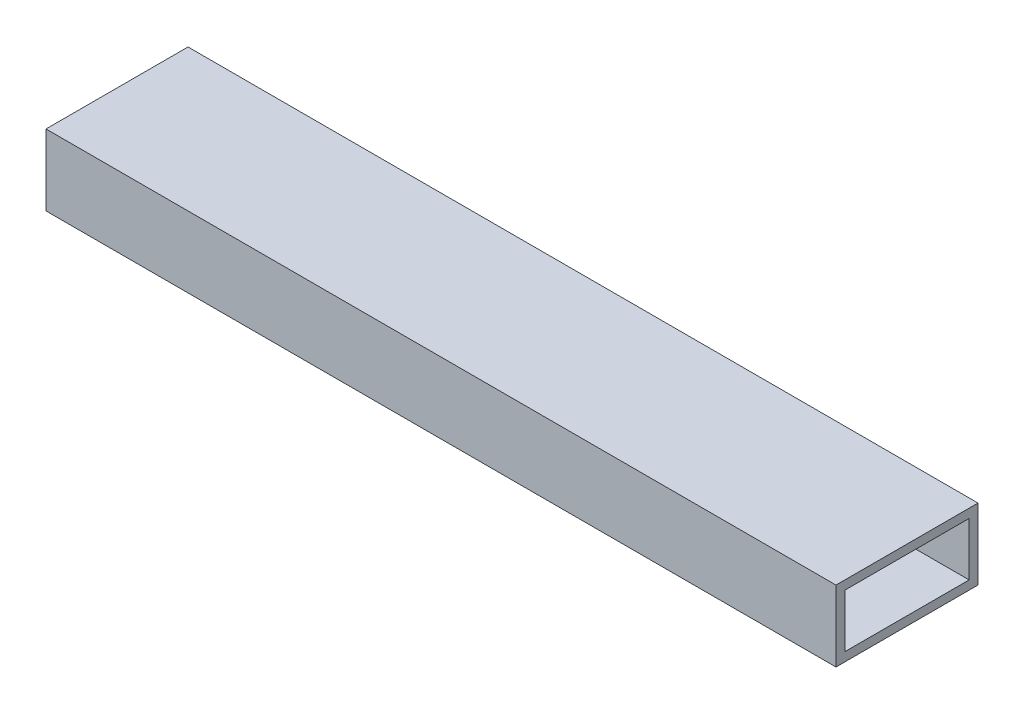
SolidWorks part; units mm, degrees
material "6061-T6 (SS)"
ref_plane "Front" through (0, 0, 0) normal (0, 0, 1) x (1, 0, 0)
ref_plane "Top" through (0, 0, 0) normal (0, 1, 0) x (1, 0, 0)
ref_plane "Right" through (0, 0, 0) normal (1, 0, 0) x (0, 0, -1)
sketch "Sketch1" plane through (0, 0, 0) normal (1, 0, 0) x (0, 0, -1)
  line L1 (-25.4, -12.7) -> (25.4, -12.7)
  line L2 (-25.4, -12.7) -> (-25.4, 12.7)
  line L3 (-25.4, 12.7) -> (25.4, 12.7)
  line L4 (25.4, -12.7) -> (25.4, 12.7)
  line L5 (-25.4, -12.7) -> (25.4, 12.7) construction
  line L6 (-25.4, 12.7) -> (25.4, -12.7) construction
  point P0 (0, 0)
  dimension "D1" = 25.4
  dimension "D2" = 50.8
extrude "Extrude-Thin1" add sketch "Sketch1" along normal blind 282.575 thin thin type one direction reverse wall 3.175
sketch "Sketch4" plane through (0, -12.7, 0) normal (0, -1, 0) x (-1, 0, 0)
  line L1 (0, -25.4) -> (0, 25.4) construction
  line L2 (-282.575, 25.4) -> (0, 25.4) construction
  line L3 (-282.575, -25.4) -> (0, -25.4) construction
  point P0 (-6.35, 15.875)
  point P2 (-31.75, -15.875)
  point P16 (-54.61, 15.875)
  point P17 (-80.01, -15.875)
  point P18 (-102.87, 15.875)
  point P19 (-128.27, -15.875)
  point P20 (-151.13, 15.875)
  point P21 (-176.53, -15.875)
  point P22 (-199.39, 15.875)
  point P23 (-224.79, -15.875)
  point P24 (-247.65, 15.875)
  point P25 (-273.05, -15.875)
  dimension "D1" = 6.35
  dimension "D2" = 9.525
  dimension "D3" = 9.525
  dimension "D4" = 25.4
  dimension "D6" = 22.86
  dimension "D5" = 6
hole_wizard "1/8 (0.13) Diameter Hole1" positions "Sketch4" profile "Sketch3" hole size "1/8" standard "ANSI Inch" end condition up to next
sketch "Sketch3" plane through (6.35, -12.7, -15.875) normal (1, 0, 0) x (0, 0, -1)
  line L0 (0, 0) -> (0, 3.175)
  line L1 (0, 3.175) -> (1.651, 3.175)
  line L2 (1.651, 3.175) -> (1.651, 0)
  line L5 (1.651, 0) -> (0, 0)
  line L11 (0, -6.35) -> (0, 107.95) construction
  dimension "Thru Hole Dia." = 3.302
  dimension "Thru Hole Depth" = 3.175
